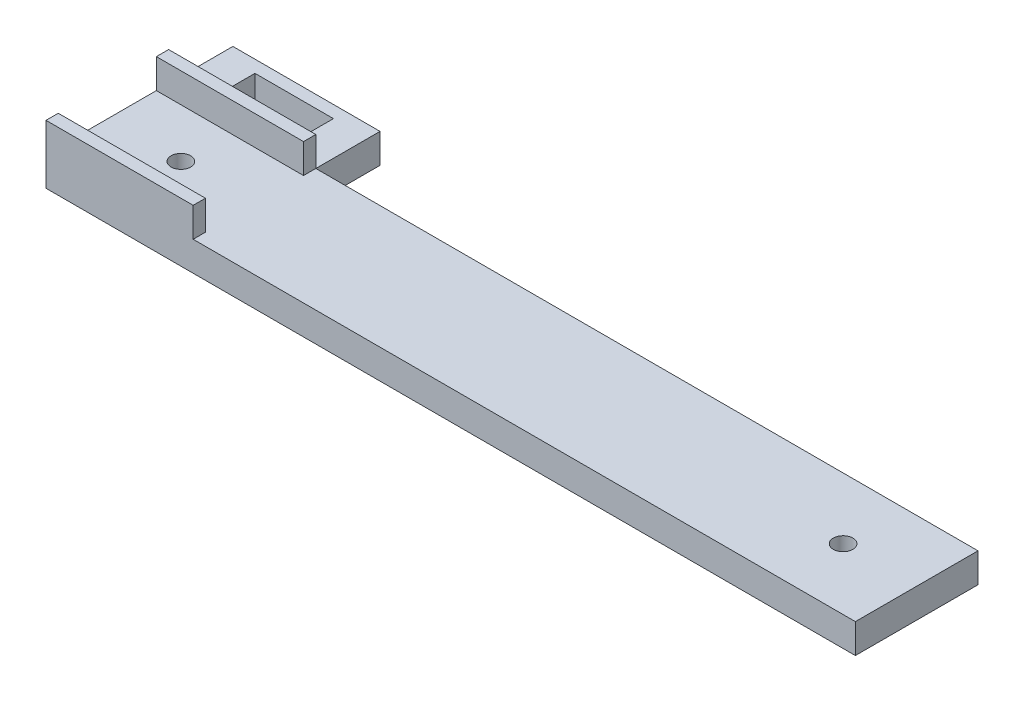
SolidWorks part; units mm, degrees
ref_plane "Front" through (0, 0, 0) normal (0, 0, 1) x (1, 0, 0)
ref_plane "Top" through (0, 0, 0) normal (0, 1, 0) x (1, 0, 0)
ref_plane "Right" through (0, 0, 0) normal (1, 0, 0) x (0, 0, -1)
sketch "Sketch1" plane through (0, 0, 0) normal (0, 1, 0) x (1, 0, 0)
  line L0 (0, -20) -> (0, -22.5)
  line L1 (0, 0) -> (-30, 0)
  line L2 (0, 0) -> (0, -20)
  line L3 (0, -20) -> (-30, -20)
  line L4 (-30, 0) -> (-30, -20)
  line L5 (0, -22.5) -> (-30, -22.5)
  line L6 (-30, -22.5) -> (-30, -20)
  line L7 (0, 0) -> (-7, 0)
  line L8 (-30, 0) -> (0, 0)
  line L9 (-30, 0) -> (-30, 2.5)
  line L10 (-30, 2.5) -> (0, 2.5)
  line L11 (0, 0) -> (0, 2.5)
  line L12 (-30, 0) -> (-23, 0)
  line L13 (-30, 2.5) -> (-30, 13.1)
  line L14 (-30, 13.1) -> (0, 13.1)
  line L15 (0, 13.1) -> (0, 2.5)
  line L16 (0, 13.1) -> (0, 15.6)
  line L17 (0, 15.6) -> (-30, 15.6)
  line L18 (-30, 15.6) -> (-30, 13.1)
  line L19 (-7, 0) -> (-7, 15.6)
  line L20 (-23, 0) -> (-23, 15.6)
  line L21 (-15, -20) -> (-15, 0)
  line L22 (-15, 0) -> (-15, -10)
  line L23 (-15, -10) -> (-165, -10)
  line L24 (-165, -10) -> (-165, -22.5)
  line L25 (-165, -22.5) -> (-165, 2.5)
  line L26 (-165, 2.5) -> (-30, 2.5)
  line L27 (-165, -22.5) -> (-30, -22.5)
  line L28 (-165, -10) -> (-150, -10)
  line L29 (135, -22.5) -> (135, 2.5)
  line L30 (135, 2.5) -> (0, 2.5)
  line L31 (135, -22.5) -> (0, -22.5)
  circle A0 centre (-150, -10) radius 2
  circle A1 centre (120, -10) radius 2
  dimension "D10" = 15
  dimension "D1" = 20
  dimension "D2" = 2.5
  dimension "D3" = 2.5
  dimension "D4" = 30
  dimension "D5" = 7
  dimension "D6" = 7
  dimension "D7" = 10.6
  dimension "D8" = 2.5
  dimension "D9" = 150
extrude "Boss-Extrude1" add sketch "Sketch1" along normal blind 6 contours L1 L8 L4 L3 L2 | L6 L5 L0 L3 | L20 L1 L19 L10 | L19 L1 L11 L10 | L8 L20 L10 L9 | L21 L23 L4 L3 | L23 L21 L8 L4 | L31 L29 L30 L11 L2 L0 A1 | L19 L10 L15 L14 | L19 L14 L16 L17 | L20 L14 L19 L17 | L14 L20 L17 L18 | L10 L20 L14 L13 region at (67.3038, 0, 10) region at (-7.5, 0, 10) region at (-15, 0, 21.25) region at (-3.5, 0, -1.25) region at (-22.5, 0, 15) region at (-15, 0, -1.25) region at (-3.5, 0, -7.8) region at (-22.5, 0, 5) region at (-3.5, 0, -14.35) region at (-26.5, 0, -1.25) region at (-26.5, 0, -7.8) region at (-15, 0, -14.35) region at (-26.5, 0, -14.35)
extrude "Boss-Extrude2" add sketch "Sketch1<3>" along normal blind 12 contours L19 L1 L11 L10 | L20 L1 L19 L10 | L6 L5 L0 L3 | L8 L20 L10 L9 region at (-15, 0, 21.25) region at (-3.5, 0, -1.25) region at (-15, 0, -1.25) region at (-26.5, 0, -1.25)
sketch "Sketch1<3>" plane through (0, 0, 0) normal (0, 1, 0) x (1, 0, 0) same geometry as "Sketch1"
sketch "Sketch3" plane through (0, 0, -15.6) normal (0, 0, -1) x (-1, 0, 0)
  line L0 (30, 3) -> (23, 3)
  line L1 (30, 6) -> (30, 0) construction
  line L2 (23, 3) -> (15, 3)
  circle A0 centre (15, 3) radius 1.5
  dimension "D1" = 7
  dimension "D2" = 8
sketch "Sketch4" plane through (0, 0, -2.5) normal (0, 0, -1) x (-1, 0, 0)
  line L0 (23, 3) -> (15, 3)
  line L1 (23, 6) -> (23, 0) construction
  line L3 (17.8868, 3) -> (16.4434, 5.5)
  line L4 (16.4434, 5.5) -> (13.5566, 5.5)
  line L5 (13.5566, 5.5) -> (12.1132, 3)
  line L6 (12.1132, 3) -> (13.5566, 0.5)
  line L7 (13.5566, 0.5) -> (16.4434, 0.5)
  line L8 (16.4434, 0.5) -> (17.8868, 3)
  circle A0 centre (15, 3) radius 2.5 construction
  dimension "D1" = 8
sketch "Sketch2" plane through (0, 6, 0) normal (0, 1, 0) x (1, 0, 0)
  line L0 (-30, -10) -> (0, -10)
  line L1 (-30, 15.6) -> (-30, 2.5) construction
  line L2 (0, 0) -> (0, -20) construction
  circle A0 centre (-15, -10) radius 2
extrude "Cut-Extrude1" cut sketch "Sketch2" against normal through all contours L0 A0 | L0 A0 region at (-15, 6, 9.1512) region at (-15, 6, 10.8488)
sketch "Sketch5" plane through (0, 0, 0) normal (0, -1, 0) x (1, 0, 0)
  line L0 (0, -2.5) -> (135, -2.5) construction
  line L1 (-20, -2.5) -> (-15, -2.5)
  line L2 (-20, -2.5) -> (-20, -18.1)
  line L3 (-20, -18.1) -> (-15, -18.1)
  line L4 (-15, -2.5) -> (-15, -18.1)
  line L5 (-30, 0) -> (-30, -2.5) construction
  line L6 (-20, -18.1) -> (-30.0231, -18.1)
  line L7 (-30.0231, -18.1) -> (-30.0231, -13.1)
  line L8 (-30.0231, -13.1) -> (-20, -13.1)
  dimension "D1" = 15.6
  dimension "D2" = 5
  dimension "D3" = 10
  dimension "D4" = 5
sketch "Sketch6" plane through (0, 0, -18.1) normal (0, 0, -1) x (-1, 0, 0)
  line L0 (15, 10) -> (15, 0) construction
  line L2 (20, 7) -> (27, 7)
  line L4 (30.0231, 0) -> (15, 0) construction
  circle A0 centre (27, 7) radius 1.25
  point P6 (0, 0)
  dimension "D3" = 7
  dimension "D1" = 5
  dimension "D2" = 7
